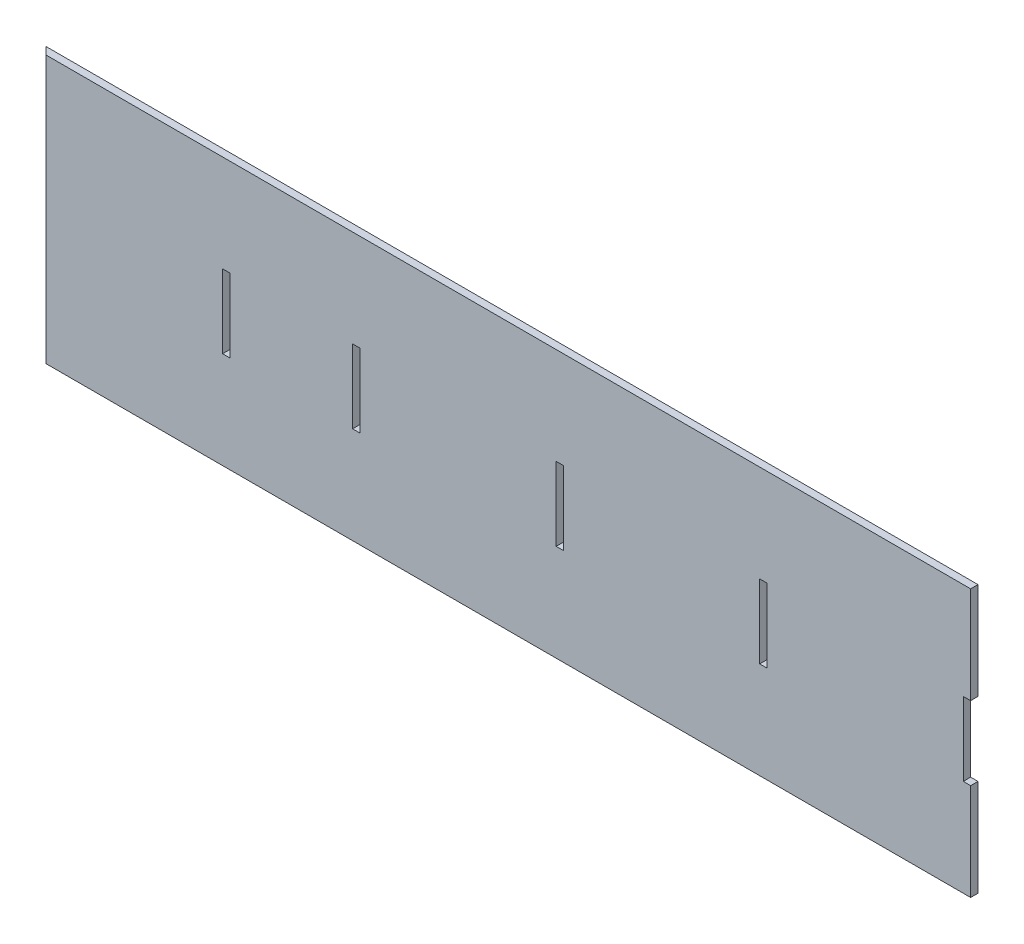
SolidWorks part; units mm, degrees
ref_plane "Front Plane" through (0, 0, 0) normal (0, 0, 1) x (1, 0, 0)
ref_plane "Top Plane" through (0, 0, 0) normal (0, 1, 0) x (1, 0, 0)
ref_plane "Right Plane" through (0, 0, 0) normal (1, 0, 0) x (0, 0, -1)
sketch "Sketch1" plane through (0, 0, 0) normal (0, 0, 1) x (1, 0, 0)
  line L1 (115, 109) -> (380, 109)
  line L3 (380, 0) -> (0, 0)
  line L5 (128, 69.5) -> (131, 69.5)
  line L6 (128, 69.5) -> (128, 39.5)
  line L7 (128, 39.5) -> (131, 39.5)
  line L8 (131, 69.5) -> (131, 39.5)
  line L14 (211, 69.5) -> (214, 69.5)
  line L15 (211, 69.5) -> (211, 39.5)
  line L16 (211, 39.5) -> (214, 39.5)
  line L17 (214, 69.5) -> (214, 39.5)
  line L18 (294, 69.5) -> (297, 69.5)
  line L19 (294, 69.5) -> (294, 39.5)
  line L20 (294, 39.5) -> (297, 39.5)
  line L21 (297, 69.5) -> (297, 39.5)
  line L22 (377, 69.5) -> (380, 69.5)
  line L23 (377, 69.5) -> (377, 39.5)
  line L24 (377, 39.5) -> (380, 39.5)
  line L55 (0, 0) -> (0, 109)
  line L56 (0, 109) -> (115, 109)
  line L57 (380, 69.5) -> (380, 109)
  line L58 (75, 69.5) -> (78, 69.5)
  line L59 (75, 69.5) -> (75, 39.5)
  line L60 (75, 39.5) -> (78, 39.5)
  line L61 (78, 69.5) -> (78, 39.5)
  line L62 (380, 39.5) -> (380, 0)
  line L63 (380, 54.5) -> (-683.0281, 54.5) construction
  point P12 (0, 0)
  point P53 (0, 0)
  point P54 (0, 0)
  dimension "D1" = 109
  dimension "D2" = 30
  dimension "D3" = 3
  dimension "D4" = 75
  dimension "D5" = 3
  dimension "D6" = 50
  dimension "D7" = 30
  dimension "D8" = 30
  dimension "D9" = 3
  dimension "D10" = 30
  dimension "D11" = 3
  dimension "D12" = 80
  dimension "D13" = 80
  dimension "D14" = 80
  dimension "D15" = 3
  dimension "D16" = 30
extrude "Boss-Extrude1" add sketch "Sketch1" along normal blind 3
chamfer "Chamfer1" distance 3 angle 45 1 edges at (0, 54.5, 3)
